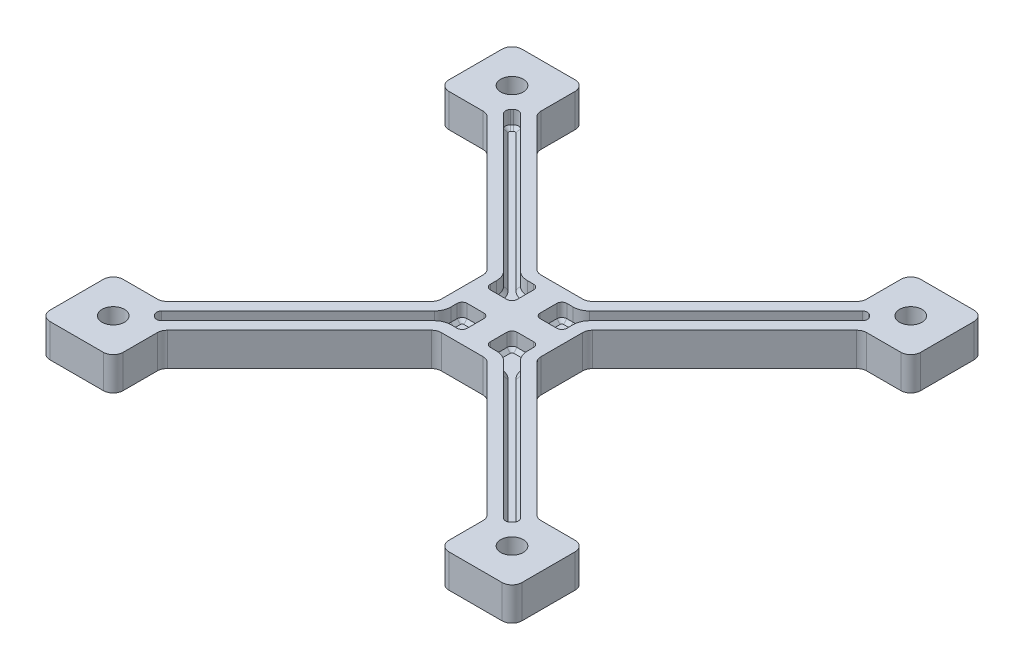
SolidWorks part; units mm, degrees
ref_plane "Front Plane" through (0, 0, 0) normal (0, 0, 1) x (1, 0, 0)
ref_plane "Top Plane" through (0, 0, 0) normal (0, 1, 0) x (1, 0, 0)
ref_plane "Right Plane" through (0, 0, 0) normal (1, 0, 0) x (0, 0, -1)
sketch "Sketch1" plane through (0, 0, 0) normal (0, 1, 0) x (1, 0, 0)
  line L0 (60, 75) -> (60, 60)
  line L1 (0, 0) -> (150, 0) construction
  line L2 (0, 0) -> (0, 150) construction
  line L3 (0, 150) -> (150, 150) construction
  line L4 (150, 0) -> (150, 150) construction
  line L5 (75, 150) -> (75, 0) construction
  line L6 (0, 75) -> (150, 75) construction
  line L7 (60, 60) -> (75, 60)
  line L8 (90, 60) -> (75, 60)
  line L9 (4, 4) -> (26, 4)
  line L10 (18.5, 26) -> (60, 67.5)
  line L11 (26, 18.5) -> (67.5, 60)
  line L12 (4, 4) -> (4, 26)
  line L13 (4, 26) -> (26, 26)
  line L14 (26, 4) -> (26, 26)
  line L15 (15, 26) -> (15, 4) construction
  line L16 (4, 15) -> (26, 15) construction
  line L17 (90, 90) -> (90, 60)
  line L18 (124, 18.5) -> (82.5, 60)
  line L19 (131.5, 26) -> (90, 67.5)
  line L20 (146, 26) -> (124, 26)
  line L21 (124, 4) -> (124, 26)
  line L22 (146, 4) -> (124, 4)
  line L23 (146, 4) -> (146, 26)
  line L24 (4, 135) -> (26, 135) construction
  line L25 (15, 124) -> (15, 146) construction
  line L26 (146, 146) -> (146, 124)
  line L27 (146, 146) -> (124, 146)
  line L28 (124, 146) -> (124, 124)
  line L29 (146, 124) -> (124, 124)
  line L30 (131.5, 124) -> (90, 82.5)
  line L31 (124, 131.5) -> (82.5, 90)
  line L32 (26, 146) -> (26, 124)
  line L33 (4, 124) -> (26, 124)
  line L34 (4, 146) -> (4, 124)
  line L35 (26, 131.5) -> (67.5, 90)
  line L36 (18.5, 124) -> (60, 82.5)
  line L37 (4, 146) -> (26, 146)
  line L38 (90, 90) -> (75, 90)
  line L39 (60, 90) -> (75, 90)
  line L40 (60, 75) -> (60, 90)
  point P4 (15, 15)
  point P5 (135, 15)
  point P6 (135, 135)
  point P7 (15, 135)
  point P12 (15, 15)
  point P20 (60, 67.5)
  point P22 (67.5, 60)
  point P47 (90, 75)
  point P444 (75, 75)
  dimension "D8" = 135
  dimension "D1" = 150
  dimension "D2" = 150
  dimension "D3" = 15
  dimension "D4" = 15
  dimension "D5" = 4
  dimension "D6" = 15
  dimension "D7" = 4
extrude "Boss-Extrude1" add sketch "Sketch1" against normal blind 10 contours L9 L14 L13 L12 | L14 L11 L7 L0 L10 L13 | L40 L0 L7 L8 L17 L38 L39 | L18 L21 L20 L19 L17 L8 | L22 L23 L20 L21 | L29 L26 L27 L28 | L38 L17 L30 L29 L28 L31 | L36 L40 L39 L35 L32 L33 | L37 L34 L33 L32 region at (75, 0, -75) region at (43, 0, -43) region at (43, 0, -107) region at (15, 0, -15) region at (15, 0, -135) region at (107, 0, -43) region at (107, 0, -107) region at (135, 0, -15) region at (135, 0, -135)
hole_wizard "1/4 Clearance Hole1" positions "Sketch2" profile "Sketch3" hole size "1/4" standard "ANSI Inch" end condition through all
sketch "Sketch2" plane through (0, 0, 0) normal (0, 1, 0) x (1, 0, 0)
  point P0 (15, 15)
  point P3 (15, 135)
  point P6 (135, 135)
  point P9 (135, 15)
sketch "Sketch3" plane through (15, 0, -15) normal (1, 0, 0) x (0, 0, 1)
  line L0 (0, 0) -> (0, 10)
  line L1 (0, 10) -> (3.3782, 10)
  line L2 (3.3782, 10) -> (3.3782, 0)
  line L5 (3.3782, 0) -> (0, 0)
  line L11 (0, -6.35) -> (0, 107.95) construction
  dimension "Thru Hole Dia." = 6.7564
  dimension "Thru Hole Depth" = 10
sketch "Sketch4" plane through (0, 0, 0) normal (0, 1, 0) x (1, 0, 0)
  line L0 (75, 90) -> (75, 60) construction
  line L1 (82.5, 90) -> (67.5, 90) construction
  line L2 (67.5, 60) -> (82.5, 60) construction
  line L3 (60, 75) -> (90, 75) construction
  line L4 (60, 67.5) -> (60, 82.5) construction
  line L5 (90, 82.5) -> (90, 67.5) construction
  line L27 (86.5, 70) -> (86.5, 68.1213)
  line L28 (85, 71.5) -> (80, 71.5)
  line L29 (78.5, 65) -> (78.5, 70)
  line L30 (81.8787, 63.5) -> (80, 63.5)
  line L31 (126.4393, 21.0104) -> (85.4142, 62.0355)
  line L32 (128.5607, 21.0104) -> (128.9896, 21.4393)
  line L33 (87.9645, 64.5858) -> (128.9896, 23.5607)
  line L34 (62.0355, 64.5858) -> (21.0104, 23.5607)
  line L35 (21.4393, 21.0104) -> (21.0104, 21.4393)
  line L36 (23.5607, 21.0104) -> (64.5858, 62.0355)
  line L37 (68.1213, 63.5) -> (70, 63.5)
  line L38 (71.5, 65) -> (71.5, 70)
  line L39 (65, 71.5) -> (70, 71.5)
  line L40 (63.5, 70) -> (63.5, 68.1213)
  line L41 (63.5, 80) -> (63.5, 81.8787)
  line L42 (65, 78.5) -> (70, 78.5)
  line L43 (71.5, 85) -> (71.5, 80)
  line L44 (68.1213, 86.5) -> (70, 86.5)
  line L45 (23.5607, 128.9896) -> (64.5858, 87.9645)
  line L46 (21.4393, 128.9896) -> (21.0104, 128.5607)
  line L47 (62.0355, 85.4142) -> (21.0104, 126.4393)
  line L59 (128.5607, 128.9896) -> (128.9896, 128.5607)
  line L60 (78.5, 85) -> (78.5, 80)
  line L61 (85, 78.5) -> (80, 78.5)
  line L67 (127.5, 142.5) -> (127.5, 130.0503)
  line L68 (142.5, 142.5) -> (127.5, 142.5)
  line L69 (142.5, 127.5) -> (142.5, 142.5)
  line L70 (130.0503, 127.5) -> (142.5, 127.5)
  line L71 (86.5, 83.9497) -> (130.0503, 127.5)
  line L72 (86.5, 67.5) -> (86.5, 83.9497)
  line L73 (83.9497, 86.5) -> (67.5, 86.5)
  line L74 (127.5, 130.0503) -> (83.9497, 86.5)
  line L79 (87.9645, 85.4142) -> (128.9896, 126.4393)
  line L80 (86.5, 80) -> (86.5, 81.8787)
  line L81 (81.8787, 86.5) -> (80, 86.5)
  line L82 (126.4393, 128.9896) -> (85.4142, 87.9645)
  arc A0 (87.9645, 85.4142) -> (86.5, 81.8787) centre (91.5, 81.8787) ccw
  arc A1 (85.4142, 87.9645) -> (81.8787, 86.5) centre (81.8787, 91.5) cw
  arc A2 (128.9896, 126.4393) -> (128.9896, 128.5607) centre (127.9289, 127.5) ccw
  arc A3 (128.5607, 128.9896) -> (126.4393, 128.9896) centre (127.5, 127.9289) ccw
  arc A4 (86.5, 80) -> (85, 78.5) centre (85, 80) cw
  arc A5 (80, 78.5) -> (78.5, 80) centre (80, 80) cw
  arc A6 (80, 86.5) -> (78.5, 85) centre (80, 85) ccw
  arc A7 (87.9645, 64.5858) -> (86.5, 68.1213) centre (91.5, 68.1213) cw
  arc A8 (86.5, 70) -> (85, 71.5) centre (85, 70) ccw
  arc A9 (80, 71.5) -> (78.5, 70) centre (80, 70) ccw
  arc A10 (80, 63.5) -> (78.5, 65) centre (80, 65) cw
  arc A11 (85.4142, 62.0355) -> (81.8787, 63.5) centre (81.8787, 58.5) ccw
  arc A12 (128.5607, 21.0104) -> (126.4393, 21.0104) centre (127.5, 22.0711) cw
  arc A13 (128.9896, 23.5607) -> (128.9896, 21.4393) centre (127.9289, 22.5) cw
  arc A14 (21.0104, 23.5607) -> (21.0104, 21.4393) centre (22.0711, 22.5) ccw
  arc A15 (21.4393, 21.0104) -> (23.5607, 21.0104) centre (22.5, 22.0711) ccw
  arc A16 (64.5858, 62.0355) -> (68.1213, 63.5) centre (68.1213, 58.5) cw
  arc A17 (70, 63.5) -> (71.5, 65) centre (70, 65) ccw
  arc A18 (70, 71.5) -> (71.5, 70) centre (70, 70) cw
  arc A19 (63.5, 70) -> (65, 71.5) centre (65, 70) cw
  arc A20 (62.0355, 64.5858) -> (63.5, 68.1213) centre (58.5, 68.1213) ccw
  arc A21 (62.0355, 85.4142) -> (63.5, 81.8787) centre (58.5, 81.8787) cw
  arc A22 (63.5, 80) -> (65, 78.5) centre (65, 80) ccw
  arc A23 (70, 78.5) -> (71.5, 80) centre (70, 80) ccw
  arc A24 (70, 86.5) -> (71.5, 85) centre (70, 85) cw
  arc A25 (64.5858, 87.9645) -> (68.1213, 86.5) centre (68.1213, 91.5) ccw
  arc A26 (21.4393, 128.9896) -> (23.5607, 128.9896) centre (22.5, 127.9289) cw
  arc A27 (21.0104, 126.4393) -> (21.0104, 128.5607) centre (22.0711, 127.5) cw
  dimension "D4" = 5
  dimension "D5" = 1.5
  dimension "D2" = 3.5
  dimension "D3" = 3.5
  dimension "D1" = 3.5
extrude "Cut-Extrude1" cut sketch "Sketch4" against normal blind 5
chamfer "Chamfer1" distance 1 angle 45 60 edges at (108.477, -5, -44.0732) (129.4289, -5, -22.5) (128.7751, -5, -21.2249) (127.5, -5, -20.5711) (105.9268, -5, -41.523) (83.7921, -5, -63.1194) (80.9393, -5, -63.5) (78.9393, -5, -63.9393) (78.5, -5, -67.5) (78.9393, -5, -71.0607) (82.5, -5, -71.5) (86.0607, -5, -71.0607) (86.5, -5, -69.0607) (86.8806, -5, -66.2079) (86.5, -5, -80.9393) (86.0607, -5, -78.9393) (82.5, -5, -78.5) (78.9393, -5, -78.9393) (78.5, -5, -82.5) (78.9393, -5, -86.0607) (80.9393, -5, -86.5) (83.7921, -5, -86.8806) (105.9268, -5, -108.477) (127.5, -5, -129.4289) (128.7751, -5, -128.7751) (129.4289, -5, -127.5) (108.477, -5, -105.9268) (86.8806, -5, -83.7921) (41.523, -5, -105.9268) (20.5711, -5, -127.5) (21.2249, -5, -128.7751) (22.5, -5, -129.4289) (44.0732, -5, -108.477) (66.2079, -5, -86.8806) (69.0607, -5, -86.5) (71.0607, -5, -86.0607) (71.5, -5, -82.5) (71.0607, -5, -78.9393) (67.5, -5, -78.5) (63.9393, -5, -78.9393) (63.5, -5, -80.9393) (63.1194, -5, -83.7921) (63.5, -5, -69.0607) (63.9393, -5, -71.0607) (67.5, -5, -71.5) (71.0607, -5, -71.0607) (71.5, -5, -67.5) (71.0607, -5, -63.9393) (69.0607, -5, -63.5) (66.2079, -5, -63.1194) (44.0732, -5, -41.523) (22.5, -5, -20.5711) (21.2249, -5, -21.2249) (20.5711, -5, -22.5) (41.523, -5, -44.0732) (63.1194, -5, -66.2079) (135, -10, -131.6218) (15, -10, -131.6218) (15, -10, -11.6218) (135, -10, -11.6218)
fillet "Fillet1" radius 3 28 edges at (67.5, -5, -90) (82.5, -5, -90) (60, -5, -82.5) (60, -5, -67.5) (67.5, -5, -60) (82.5, -5, -60) (90, -5, -67.5) (90, -5, -82.5) (146, -5, -146) (131.5, -5, -124) (124, -5, -146) (146, -5, -124) (124, -5, -131.5) (18.5, -5, -124) (26, -5, -131.5) (26, -5, -146) (4, -5, -124) (4, -5, -146) (4, -5, -26) (18.5, -5, -26) (4, -5, -4) (26, -5, -18.5) (26, -5, -4) (124, -5, -18.5) (131.5, -5, -26) (146, -5, -26) (124, -5, -4) (146, -5, -4)
